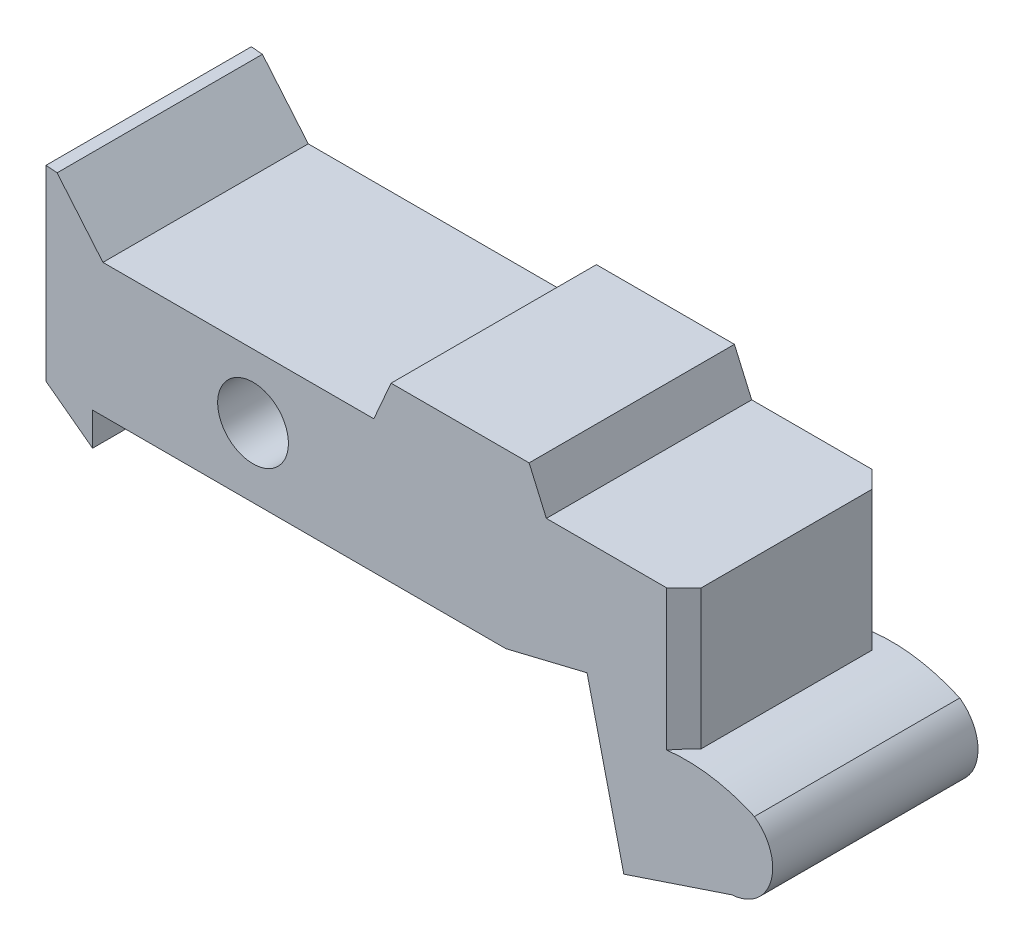
SolidWorks part; units mm, degrees
ref_plane "정면" through (0, 0, 0) normal (0, 0, 1) x (1, 0, 0)
ref_plane "윗면" through (0, 0, 0) normal (0, 1, 0) x (1, 0, 0)
ref_plane "우측면" through (0, 0, 0) normal (1, 0, 0) x (0, 0, -1)
sketch "스케치1" plane through (0, 0, 0) normal (0, 0, 1) x (1, 0, 0)
  line L0 (-9.3, -4) -> (-9.3, -5.9163)
  line L1 (-9.3, -4) -> (13.9925, -4)
  line L2 (0, 0) -> (20, 0) construction
  line L3 (-8.7, 3.7127) -> (7, 3.7127)
  line L4 (24.9748, -4.3645) -> (24.9748, 3.7127)
  line L5 (-2.0156, -0.3742) -> (20, 3.7127) construction
  line L6 (-2.0102, 0.402) -> (2.0102, -0.402) construction
  line L7 (-9.3, -5.9163) -> (-12, -3.9065)
  line L8 (-12, -3.9065) -> (-12, 4.1457)
  line L9 (17, 3.7127) -> (16, 6)
  line L10 (16, 6) -> (8, 6)
  line L11 (8, 6) -> (7, 3.7127)
  line L12 (17, 3.7127) -> (20, 3.7127)
  line L13 (19.3575, -2.8587) -> (21.4883, -11.8995)
  line L15 (21.4883, -11.8995) -> (27.7467, -9.8088)
  line L16 (24.9748, 3.7127) -> (20, 3.7127)
  line L17 (13.9925, -4) -> (14.657, -4)
  line L18 (14.657, -4) -> (19.3575, -2.8587)
  line L21 (-12, 4.1457) -> (-12, 7.6457)
  line L22 (-12, 7.6457) -> (-8.7, 3.7127)
  circle A0 centre (0, 0) radius 2.05
  arc A1 (24.9748, -4.3645) -> (29.0593, -5.222) centre (25.0886, -13.9791) cw
  arc A2 (29.0593, -5.222) -> (27.7467, -9.8088) centre (27.5853, -7.2814) cw
  dimension "D1" = 4.1
  dimension "D2" = 3.5
  dimension "D3" = 20
  dimension "D4" = 12
  dimension "D5" = 2.7
  dimension "D6" = 10
  dimension "D7" = 8
  dimension "D8" = 3
  dimension "D9" = 3.3
  dimension "D10" = 6
extrude "보스-돌출1" add sketch "스케치1" along normal mid plane 11.9
sketch "스케치2" plane through (0, -4, 0) normal (0, -1, 0) x (1, 0, 0)
  line L0 (0, 0) -> (13, 0) construction
  circle A0 centre (13, 0) radius 5
  circle A1 centre (13, 0) radius 4.3
  dimension "D1" = 10
  dimension "D2" = 8.6
  dimension "D3" = 13
extrude "컷-돌출1" cut sketch "스케치2" against normal blind 3
fillet "필렛1" radius 1 1 edges at (8.7, -4, 0)
chamfer "모따기2" distance 1 angle 45 2 edges at (24.9748, -0.3259, -5.95) (24.9748, -0.3259, 5.95)
chamfer "모따기3" distance 1 angle 45 1 edges at (-12, 7.6457, 0) first distance on face at (-10.35, 5.6792, 0)
